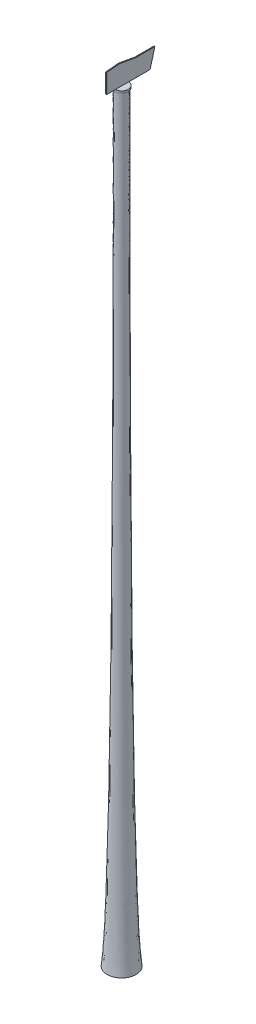
SolidWorks part; units mm, degrees
ref_plane "Ebene vorne" through (0, 0, 0) normal (0, 0, 1) x (1, 0, 0)
ref_plane "Ebene oben" through (0, 0, 0) normal (0, 1, 0) x (1, 0, 0)
ref_plane "Ebene rechts" through (0, 0, 0) normal (1, 0, 0) x (0, 0, -1)
sketch "Skizze2" plane through (0, 0, 0) normal (1, 0, 0) x (0, 0, -1)
  line L0 (500, -1000) -> (500, 1000)
  line L1 (-500, -500) -> (500, -500) construction
  line L2 (-500, -500) -> (-500, 500) construction
  line L3 (-500, 500) -> (500, 500) construction
  line L4 (500, -500) -> (500, 500) construction
  line L5 (-500, -500) -> (500, 500) construction
  line L6 (-500, 500) -> (500, -500) construction
  line L7 (500, 1000) -> (1850, 1118.1097)
  line L8 (1850, 1118.1097) -> (3500, 827.1702)
  line L9 (3500, 827.1702) -> (5500, 827.1702)
  line L10 (5500, 827.1702) -> (5010.4112, -1000)
  line L11 (5010.4112, -1000) -> (500, -1000)
  point P0 (0, 0)
  dimension "D1" = 1000
  dimension "D2" = 1000
  dimension "D3" = 95
  dimension "D4" = 165
  dimension "D5" = 75
  dimension "D6" = 1350
  dimension "D7" = 1650
  dimension "D8" = 5000
  dimension "D9" = 500
  dimension "D10" = 500
extrude "Aufsatz-Linear austragen1" add sketch "Skizze2" along normal blind 50 and the other way blind 50
fillet "Verrundung1" radius 10 18 edges at (0, -1000, -5010.4112) (-50, -86.4149, -5255.2056) (-50, -1000, -2755.2056) (-50, 0, -500) (0, -1000, -500) (50, 0, -500) (50, -86.4149, -5255.2056) (50, -1000, -2755.2056) (-50, 827.1702, -4500) (0, 827.1702, -5500) (50, 827.1702, -4500) (-50, 972.6399, -2675) (0, 827.1702, -3500) (50, 972.6399, -2675) (-50, 1059.0548, -1175) (0, 1118.1097, -1850) (50, 1059.0548, -1175) (0, 1000, -500)
sketch "Skizze3" plane through (0, 0, 0) normal (1, 0, 0) x (0, 0, -1)
  line L0 (2100, 0) -> (2100, -215.2925) construction
  line L1 (2100, -990) -> (1400, -990)
  line L2 (510, -990) -> (5002.738, -990) construction
  line L3 (1400, -990) -> (1400, -1190)
  line L4 (1400, -1190) -> (1450, -1190)
  line L5 (1450, -1190) -> (1450, -1000)
  line L6 (5002.738, -1000) -> (510, -1000) construction
  line L7 (1450, -1000) -> (1480, -1000)
  line L8 (1480, -1000) -> (1480, -1190)
  line L9 (2100, -990) -> (2100, -80000)
  line L10 (600, -80000) -> (2100, -80000)
  line L11 (-37.4147, 0) -> (55.262, 0) construction
  line L13 (500, -990) -> (500, 990.8367) construction
  line L14 (1400, -1190) -> (161.2362, -1190) construction
  spline S0 degree 3 poles (1480, -1190) (1480, -1545.3967) (1606.4483, -71462.3731) (600, -80000) knots 0 0 0 0 1 1 1 1
  dimension "D1" = 200
  dimension "D2" = 1600
  dimension "D3" = 700
  dimension "D4" = 50
  dimension "D5" = 30
  dimension "D6" = 750
  dimension "D7" = 80000
  dimension "D8" = 48000
  dimension "D9" = 1500
revolve "Rotation1" add sketch "Skizze3" angle 360 about L0
